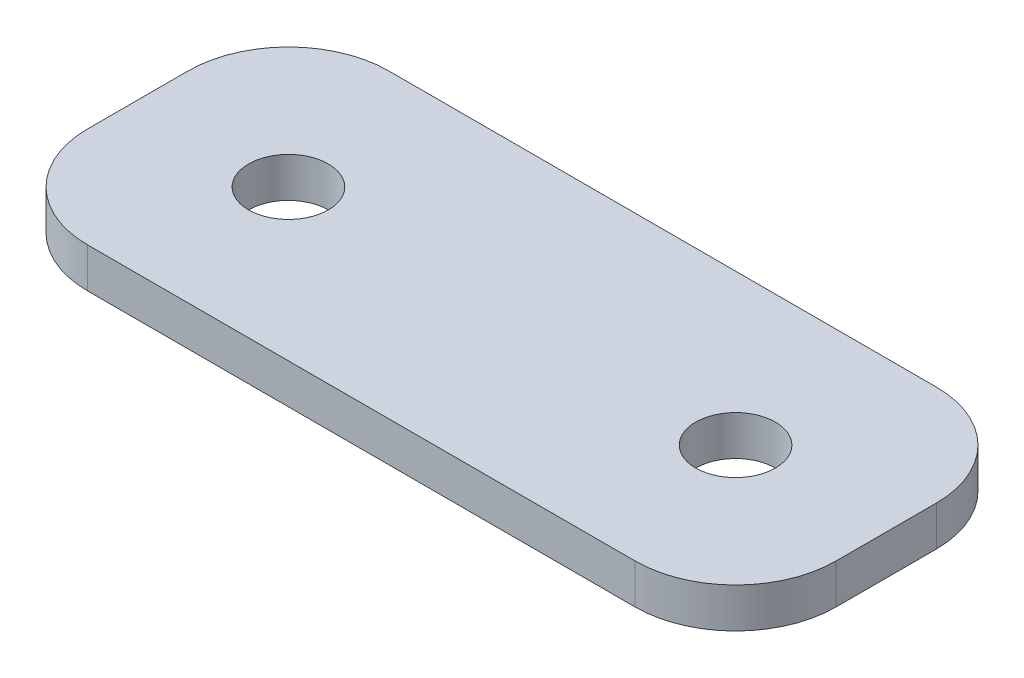
SolidWorks part; units mm, degrees
ref_plane "Front Plane" through (0, 0, 0) normal (0, 0, 1) x (1, 0, 0)
ref_plane "Top Plane" through (0, 0, 0) normal (0, 1, 0) x (1, 0, 0)
ref_plane "Right Plane" through (0, 0, 0) normal (1, 0, 0) x (0, 0, -1)
sketch "Sketch1" plane through (0, 0, 0) normal (0, 1, 0) x (1, 0, 0)
  line L0 (-8.905, 0) -> (8.905, 0) construction
  line L1 (14.905, -6) -> (-14.905, -6)
  line L2 (14.905, -6) -> (14.905, 6)
  line L3 (14.905, 6) -> (-14.905, 6)
  line L4 (-14.905, -6) -> (-14.905, 6)
  line L5 (14.905, -6) -> (-14.905, 6) construction
  line L6 (14.905, 6) -> (-14.905, -6) construction
  circle A0 centre (-8.905, 0) radius 1.5875
  circle A1 centre (8.905, 0) radius 1.5875
  circle A2 centre (-8.905, 0) radius 5 construction
  point P0 (0, 0)
  point P8 (0, 0)
  dimension "D1" = 3.175
  dimension "D4" = 10
  dimension "D2" = 17.81
  dimension "D3" = 12
  dimension "D5" = 6
extrude "Boss-Extrude1" add sketch "Sketch1" along normal mid plane 1.5875
sketch "Sketch2" plane through (0, -0.7937, 0) normal (0, -1, 0) x (1, 0, 0)
  line L0 (8.905, 0) -> (-8.905, 0) construction
fillet "Fillet1" radius 4 4 edges at (-14.905, 0, -6) (-14.905, 0, 6) (14.905, 0, 6) (14.905, 0, -6)
